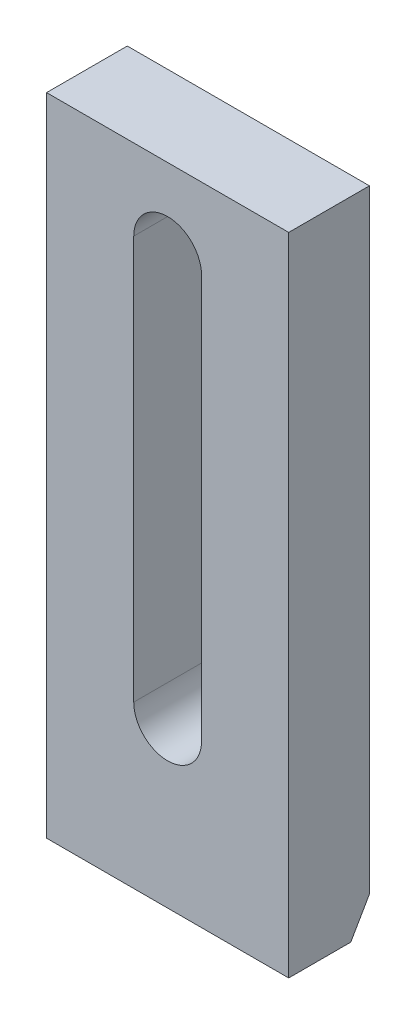
SolidWorks part; units mm, degrees
ref_plane "Спереди" through (0, 0, 0) normal (0, 0, 1) x (1, 0, 0)
ref_plane "Сверху" through (0, 0, 0) normal (0, 1, 0) x (1, 0, 0)
ref_plane "Справа" through (0, 0, 0) normal (1, 0, 0) x (0, 0, -1)
sketch "Эскиз1" plane through (0, 0, 0) normal (0, 0, 1) x (1, 0, 0)
  line L1 (0, 0) -> (75, 0)
  line L2 (0, 0) -> (0, 200)
  line L3 (0, 200) -> (75, 200)
  line L4 (75, 0) -> (75, 200)
  dimension "D1" = 75
  dimension "D2" = 200
extrude "Бобышка-Вытянуть1" add sketch "Эскиз1" along normal blind 25
sketch "Эскиз2" plane through (0, 0, 25) normal (0, 0, 1) x (1, 0, 0)
  line L1 (27, 50) -> (27, 175)
  line L2 (48, 50) -> (48, 175)
  line L3 (0, 200) -> (0, 0) construction
  line L4 (0, 0) -> (75, 0) construction
  arc A0 (27, 50) -> (48, 50) centre (37.5, 50) ccw
  arc A1 (27, 175) -> (48, 175) centre (37.5, 175) cw
  point P7 (27, 112.5)
  point P10 (48, 112.5)
  dimension "D1" = 37.5
  dimension "D2" = 50
extrude "Вырез-Вытянуть1" cut sketch "Эскиз2" against normal through all
chamfer "Фаска1" distance 10 angle 30 1 edges at (37.5, 0, 0) first distance on face at (37.5, 112.5, 0)
